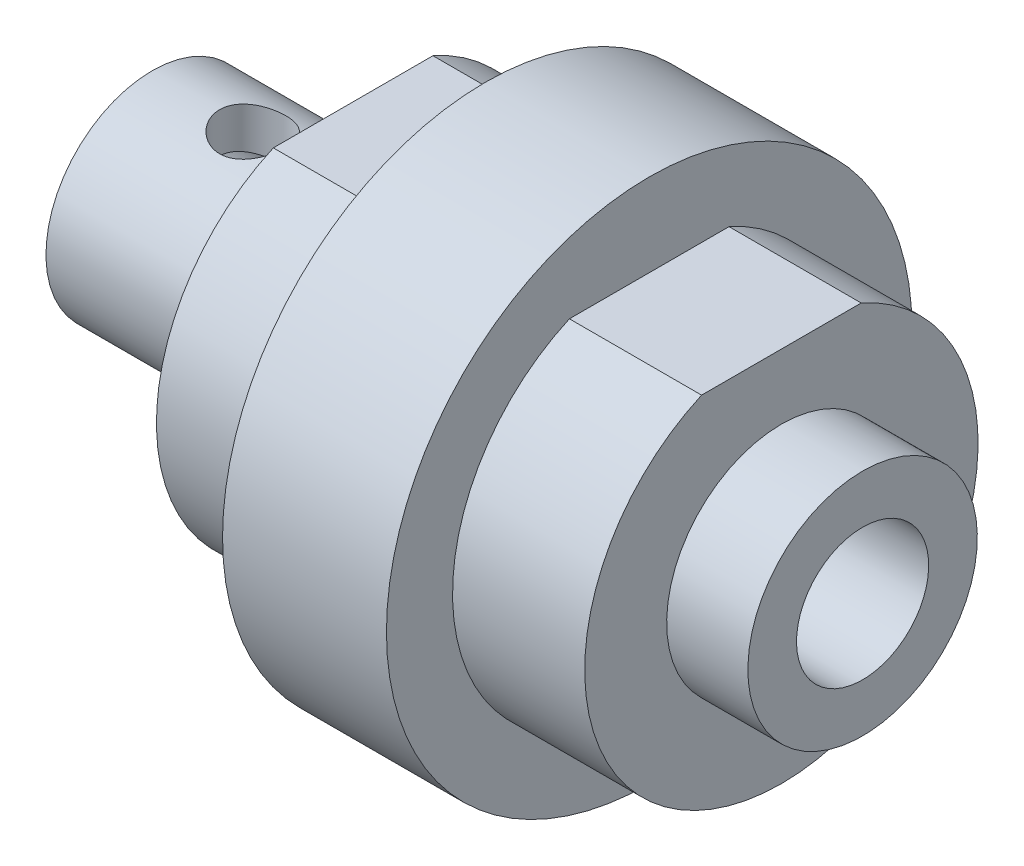
SolidWorks part; units mm, degrees
ref_plane "Front Plane" through (0, 0, 0) normal (0, 0, 1) x (1, 0, 0)
ref_plane "Top Plane" through (0, 0, 0) normal (0, 1, 0) x (1, 0, 0)
ref_plane "Right Plane" through (0, 0, 0) normal (1, 0, 0) x (0, 0, -1)
sketch "Sketch1" plane through (0, 0, 0) normal (0, 0, 1) x (1, 0, 0)
  line L0 (0, 0) -> (0, 5.1054)
  line L1 (0, 5.1054) -> (9.652, 5.1054)
  line L2 (9.652, 5.1054) -> (9.652, 9.4488)
  line L3 (9.652, 9.4488) -> (16.002, 9.4488)
  line L4 (16.002, 9.4488) -> (16.002, 12.6238)
  line L5 (16.002, 12.6238) -> (23.876, 12.6238)
  line L6 (23.876, 12.6238) -> (23.876, 9.4488)
  line L7 (23.876, 9.4488) -> (30.226, 9.4488)
  line L8 (30.226, 9.4488) -> (30.226, 5.5118)
  line L9 (30.226, 5.5118) -> (34.1274, 5.5118)
  line L10 (34.1274, 5.5118) -> (34.1274, 0)
  line L11 (34.1274, 0) -> (0, 0)
  line L12 (34.1274, 3.175) -> (0, 3.175)
  line L13 (34.1274, 0) -> (34.1274, 3.175)
  dimension "D1" = 9.652
  dimension "D2" = 6.35
  dimension "D3" = 7.874
  dimension "D4" = 6.35
  dimension "D5" = 3.9014
  dimension "D6" = 3.937
  dimension "D7" = 3.175
  dimension "D8" = 3.175
  dimension "D9" = 5.1054
  dimension "D11" = 3.175
  dimension "D12" = 5.5118
revolve "Revolve1" add sketch "Sketch1" angle 360 about L11 region at (19.0039, 6.6402, 0)
sketch "Sketch2" plane through (0, 0, 0) normal (0, 0, 1) x (1, 0, 0)
  line L4 (16.002, 9.4488) -> (9.652, 9.4488)
  line L5 (23.876, 9.4488) -> (23.876, 8.636)
  line L6 (23.876, 8.636) -> (30.226, 8.636)
  line L7 (30.226, 8.636) -> (30.226, 9.4488)
  line L8 (30.226, 9.4488) -> (23.876, 9.4488)
  line L9 (9.652, 9.4488) -> (9.652, 8.636)
  line L10 (9.652, 9.4488) -> (9.652, -9.4488) construction
  line L11 (9.652, 8.636) -> (16.002, 8.636)
  line L12 (16.002, 9.4488) -> (16.002, -9.4488) construction
  line L13 (16.002, 8.636) -> (16.002, 9.4488)
  point P14 (30.226, 9.4488)
  dimension "D1" = 0.8128
  dimension "D2" = 6.35
extrude "Cut-Extrude1" cut sketch "Sketch2" against normal through all both and the other way through all
sketch "Sketch3" plane through (0, 0, 0) normal (0, 1, 0) x (1, 0, 0)
  line L0 (9.652, 5.1054) -> (0, 5.1054) construction
  circle A0 centre (4.826, 0) radius 1.5875
  dimension "D1" = 3.175
  dimension "D2" = 4.826
  dimension "D3" = 5.1054
extrude "Cut-Extrude2" cut sketch "Sketch3" against normal through all and the other way through all
